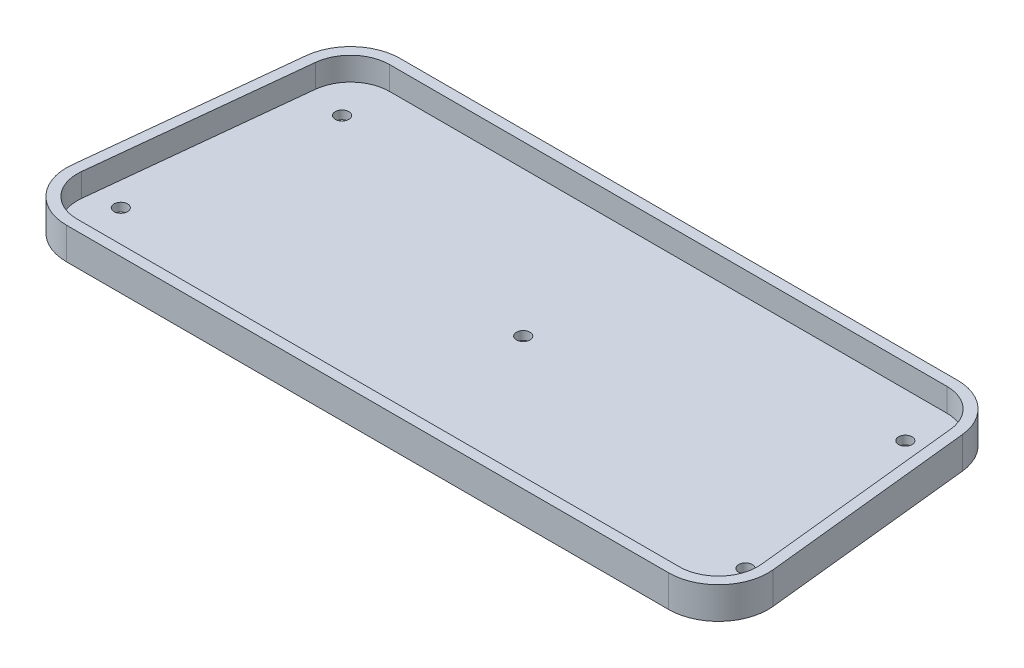
SolidWorks part; units mm, degrees
ref_plane "Front Plane" through (0, 0, 0) normal (0, 0, 1) x (1, 0, 0)
ref_plane "Top Plane" through (0, 0, 0) normal (0, 1, 0) x (1, 0, 0)
ref_plane "Right Plane" through (0, 0, 0) normal (1, 0, 0) x (0, 0, -1)
sketch "Sketch1" plane through (0, 0, 0) normal (0, 1, 0) x (1, 0, 0)
  line L24 (-101.1965, 62.2698) -> (-107.9313, -1.2302)
  line L25 (-96.2493, -14.2167) -> (84.3616, -14.2167)
  line L26 (96.0435, -1.2302) -> (89.3087, 62.2698)
  line L27 (77.6267, 72.7783) -> (-89.5145, 72.7783)
  line L28 (-101.1965, 62.2698) -> (-107.9313, -1.2302)
  line L29 (-96.2493, -14.2167) -> (84.3616, -14.2167)
  line L30 (96.0435, -1.2302) -> (89.3087, 62.2698)
  line L31 (77.6267, 72.7783) -> (-89.5145, 72.7783)
  arc A24 (-107.9313, -1.2302) -> (-96.2493, -14.2167) centre (-96.2493, -2.4692) ccw
  arc A25 (84.3616, -14.2167) -> (96.0435, -1.2302) centre (84.3616, -2.4692) ccw
  arc A26 (89.3087, 62.2698) -> (77.6267, 72.7783) centre (77.6267, 61.0308) ccw
  arc A27 (-89.5145, 72.7783) -> (-101.1965, 62.2698) centre (-89.5145, 61.0308) ccw
  arc A28 (-107.9313, -1.2302) -> (-96.2493, -14.2167) centre (-96.2493, -2.4692) ccw
  arc A29 (84.3616, -14.2167) -> (96.0435, -1.2302) centre (84.3616, -2.4692) ccw
  arc A30 (89.3087, 62.2698) -> (77.6267, 72.7783) centre (77.6267, 61.0308) ccw
  arc A31 (-89.5145, 72.7783) -> (-101.1965, 62.2698) centre (-89.5145, 61.0308) ccw
  circle A68 centre (78.5238, 59.4103) radius 2.032 construction
  circle A69 centre (87.7313, 2.2603) radius 2.032 construction
  circle A70 centre (-5.9439, 29.2808) radius 2.032 construction
  circle A71 centre (-99.6191, 2.2603) radius 2.032 construction
  circle A72 centre (-90.4116, 59.4103) radius 2.032 construction
  circle A73 centre (78.5238, 59.4103) radius 2.032
  circle A74 centre (87.7313, 2.2603) radius 2.032
  circle A75 centre (-5.9439, 29.2808) radius 2.032
  circle A76 centre (-99.6191, 2.2603) radius 2.032
  circle A77 centre (-90.4116, 59.4103) radius 2.032
  dimension "D1" = 1.5875
extrude "Boss-Extrude1" add sketch "Sketch1" along normal blind 2.54
sketch "Sketch4" plane through (0, 0, 0) normal (0, -1, 0) x (1, 0, 0)
  line L0 (77.6267, -72.7783) -> (-89.5145, -72.7783) construction
  line L1 (77.6267, -72.7783) -> (-89.5145, -72.7783)
  line L2 (-101.1965, -62.2698) -> (-107.9313, 1.2302) construction
  line L3 (-96.2493, 14.2167) -> (84.3616, 14.2167) construction
  line L4 (96.0435, 1.2302) -> (89.3087, -62.2698) construction
  line L5 (-101.1965, -62.2698) -> (-107.9313, 1.2302)
  line L6 (-96.2493, 14.2167) -> (84.3616, 14.2167)
  line L7 (96.0435, 1.2302) -> (89.3087, -62.2698)
  line L8 (99.2008, 0.8953) -> (92.466, -62.6047)
  line L9 (77.6267, -75.9533) -> (-89.5145, -75.9533)
  line L10 (-104.3538, -62.6047) -> (-111.0886, 0.8953)
  line L11 (-96.2493, 17.3917) -> (84.3616, 17.3917)
  arc A0 (-101.1965, -62.2698) -> (-89.5145, -72.7783) centre (-89.5145, -61.0308) ccw construction
  arc A1 (-101.1965, -62.2698) -> (-89.5145, -72.7783) centre (-89.5145, -61.0308) ccw
  arc A2 (-96.2493, 14.2167) -> (-107.9313, 1.2302) centre (-96.2493, 2.4692) ccw construction
  arc A3 (96.0435, 1.2302) -> (84.3616, 14.2167) centre (84.3616, 2.4692) ccw construction
  arc A4 (77.6267, -72.7783) -> (89.3087, -62.2698) centre (77.6267, -61.0308) ccw construction
  arc A5 (-96.2493, 14.2167) -> (-107.9313, 1.2302) centre (-96.2493, 2.4692) ccw
  arc A6 (96.0435, 1.2302) -> (84.3616, 14.2167) centre (84.3616, 2.4692) ccw
  arc A7 (77.6267, -72.7783) -> (89.3087, -62.2698) centre (77.6267, -61.0308) ccw
  arc A8 (77.6267, -75.9533) -> (92.466, -62.6047) centre (77.6267, -61.0308) ccw
  arc A9 (-104.3538, -62.6047) -> (-89.5145, -75.9533) centre (-89.5145, -61.0308) ccw
  arc A10 (-96.2493, 17.3917) -> (-111.0886, 0.8953) centre (-96.2493, 2.4692) ccw
  arc A11 (99.2008, 0.8953) -> (84.3616, 17.3917) centre (84.3616, 2.4692) ccw
  arc M9 (-101.1965, -62.2698) -> (-89.5145, -72.7783) centre (-89.5145, -61.0308) ccw
  line M10 (-89.5145, -72.7783) -> (77.6267, -72.7783)
  arc M11 (77.6267, -72.7783) -> (89.3087, -62.2698) centre (77.6267, -61.0308) ccw
  line M12 (89.3087, -62.2698) -> (96.0435, 1.2302)
  arc M13 (96.0435, 1.2302) -> (84.3616, 14.2167) centre (84.3616, 2.4692) ccw
  line M14 (84.3616, 14.2167) -> (-96.2493, 14.2167)
  arc M15 (-96.2493, 14.2167) -> (-107.9313, 1.2302) centre (-96.2493, 2.4692) ccw
  line M16 (-107.9313, 1.2302) -> (-101.1965, -62.2698)
  dimension "D1" = 3.175
  dimension "D2" = 3.175
extrude "Boss-Extrude2" add sketch "Sketch4" against normal blind 9.525 contours L8 A11 L11 A10 L10 A9 L9 A8 M9 M16 M15 M14 M13 M12 M11 M10 region at (93.544, 0, -30.6119)
